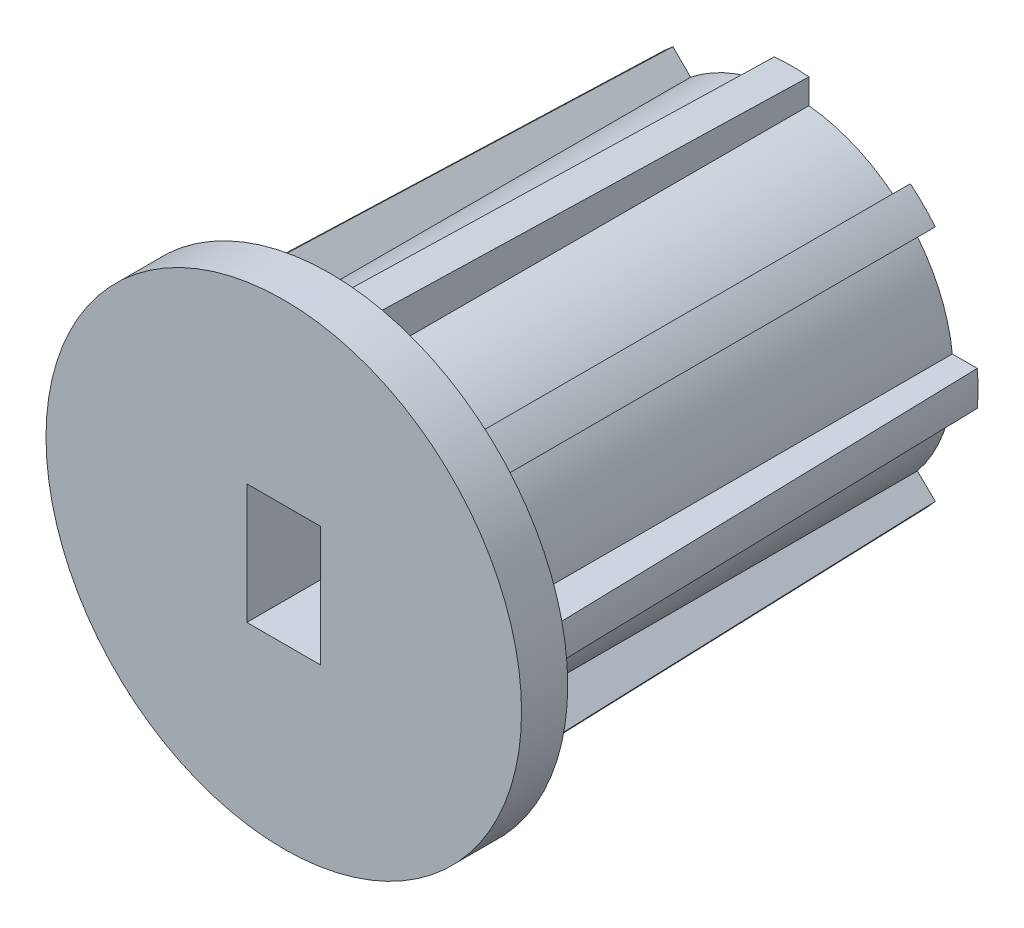
SolidWorks part; units mm, degrees
ref_plane "Спереди" through (0, 0, 0) normal (0, 0, 1) x (1, 0, 0)
ref_plane "Сверху" through (0, 0, 0) normal (0, 1, 0) x (1, 0, 0)
ref_plane "Справа" through (0, 0, 0) normal (1, 0, 0) x (0, 0, -1)
ref_axis "Ось1" through (-88.99, 0, 0) along (1, 0, 0)
ref_axis "Ось2" through (0, 55, 0) along (0, -1, 0)
ref_axis "Ось3" through (0, 0, 55) along (0, 0, -1)
sketch "Эскиз1" plane through (0, 0, 0) normal (0, 0, 1) x (1, 0, 0)
  circle A0 centre (0, 0) radius 20.6
extrude "Бобышка-Вытянуть1" add sketch "Эскиз1" along normal blind 4
sketch "Эскиз2" plane through (0, 0, 0) normal (0, 0, 1) x (1, 0, 0)
  circle A0 centre (0, 0) radius 14
  circle A1 centre (0, 0) radius 10
extrude "Бобышка-Вытянуть2" add sketch "Эскиз2" along normal blind 1 and the other way blind 40 separate body
sketch "Эскиз3" plane through (0, 0, 0) normal (0, 0, -1) x (-1, 0, 0)
  line L0 (-17.1345, 1.5) -> (-13.9194, 1.5)
  line L1 (88.99, 0) -> (-88.99, 0) construction
  line L2 (-1.5, 17.1345) -> (-1.5, 13.9194)
  line L3 (0, 55) -> (0, -55) construction
  line L4 (0, 16.8) -> (0, -16.8) construction
  line L5 (-13.1986, 11.0289) -> (-10.8944, 8.7928)
  line L6 (-11.0277, 13.1996) -> (-8.7538, 10.9257)
  line L7 (1.5, 17.1345) -> (1.5, 13.9194)
  line L8 (11.0277, 13.1996) -> (8.7538, 10.9257)
  line L9 (13.1986, 11.0289) -> (10.8944, 8.7928)
  line L10 (17.1345, 1.5) -> (13.9194, 1.5)
  line L11 (-21.419, 0) -> (19.2104, 0) construction
  line L12 (17.1345, -1.5) -> (13.9194, -1.5)
  line L13 (13.1986, -11.0289) -> (10.8944, -8.7928)
  line L14 (11.0277, -13.1996) -> (8.7538, -10.9257)
  line L15 (1.5, -17.1345) -> (1.5, -13.9194)
  line L16 (-1.5, -17.1345) -> (-1.5, -13.9194)
  line L17 (-11.0277, -13.1996) -> (-8.7538, -10.9257)
  line L18 (-13.1986, -11.0289) -> (-10.8944, -8.7928)
  line L19 (-17.1345, -1.5) -> (-13.9194, -1.5)
  arc A0 (-17.1345, -1.5) -> (-17.1345, 1.5) centre (0, 0) cw
  circle A1 centre (0, 0) radius 14 construction
  arc A2 (-13.1986, 11.0289) -> (-11.0277, 13.1996) centre (0, 0) cw
  arc A3 (-1.5, 17.1345) -> (1.5, 17.1345) centre (0, 0) cw
  arc A4 (13.1986, 11.0289) -> (11.0277, 13.1996) centre (0, 0) ccw
  arc A5 (17.1345, -1.5) -> (17.1345, 1.5) centre (0, 0) ccw
  arc A6 (13.1986, -11.0289) -> (11.0277, -13.1996) centre (0, 0) cw
  arc A7 (-1.5, -17.1345) -> (1.5, -17.1345) centre (0, 0) ccw
  arc A8 (-13.1986, -11.0289) -> (-11.0277, -13.1996) centre (0, 0) ccw
  circle A9 centre (0, 0) radius 14
  dimension "D2" = 1.5
  dimension "D1" = 1.5
extrude "Бобышка-Вытянуть3" add sketch "Эскиз3" along direction (0, 0, 1) on the side of the normal blind 40 contours A9 L18 A8 L17 | A9 L16 A7 L15 | A9 L14 A6 L13 | A9 L12 A5 L10 | A9 L9 A4 L8 | A9 L7 A3 L2 | A9 L6 A2 L5 | A9 L0 A0 L19 region at (15.5756, 0, 0) region at (11.007, 11.0252, 0) region at (11.007, -11.0252, 0) region at (0, 15.5756, 0) region at (0, -15.5756, 0) region at (-11.007, 11.0252, 0) region at (-11.007, -11.0252, 0) region at (-15.5756, 0, 0)
sketch "Эскиз8" plane through (0, 0, 0) normal (1, 0, 0) x (0, 0, -1)
  line L0 (40, 16.1526) -> (0, 17.2)
  line L3 (40, 17.1345) -> (40, 13.9194) construction
  line L5 (0, 0) -> (46.6699, 0) construction
  line L6 (0, 17.2) -> (40, 17.2)
  line L8 (40, 17.2) -> (40, 16.1526)
  point P4 (0, 17.1345)
  point P5 (0, 0)
  point P8 (15, 17.2)
  point P11 (30, 17.2)
  point P12 (30, 17.2)
  point P13 (15, 17.2)
  point P14 (15, 17.2)
  point P16 (0, 0)
  point P17 (0, 17.1345)
  point P20 (0, 17.2)
  point P22 (30, 16.5665)
  point P23 (30, 16.0208)
  point P24 (29.957, 18.8904)
  point P27 (30, 17.2)
  point P28 (30, 17.2)
  dimension "D1" = 1.5
revolve "Вырез-Повернуть2" cut sketch "Эскиз8" angle 360 about L5
sketch "Эскиз9" plane through (0, 0, 0) normal (0, 0, -1) x (-1, 0, 0)
  circle A0 centre (0, 0) radius 14
extrude "Бобышка-Вытянуть4" add sketch "Эскиз9" along normal blind 14
sketch "Эскиз10" plane through (0, 0, 4) normal (0, 0, 1) x (1, 0, 0)
  line L1 (3.2, 5.2) -> (-3.2, 5.2)
  line L2 (3.2, 5.2) -> (3.2, -5.2)
  line L3 (3.2, -5.2) -> (-3.2, -5.2)
  line L4 (-3.2, 5.2) -> (-3.2, -5.2)
  line L5 (3.2, 5.2) -> (-3.2, -5.2) construction
  line L6 (3.2, -5.2) -> (-3.2, 5.2) construction
  point P0 (0, 0)
  dimension "D1" = 10.4
  dimension "D2" = 6.4
extrude "Вырез-Вытянуть1" cut sketch "Эскиз10" against normal blind 12
scale "Масштаб1" bodies to scale 108 scale about centroid uniform scaling yes scale factor 0.5
